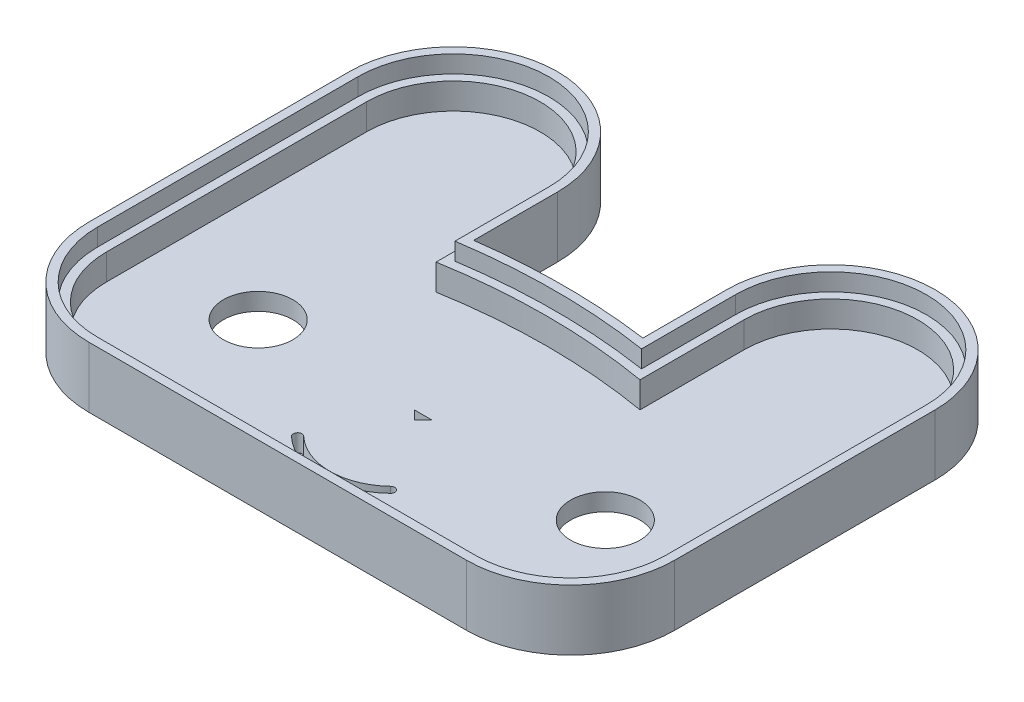
SolidWorks part; units mm, degrees
ref_plane "前视基准面" through (0, 0, 0) normal (0, 0, 1) x (1, 0, 0)
ref_plane "上视基准面" through (0, 0, 0) normal (0, 1, 0) x (1, 0, 0)
ref_plane "右视基准面" through (0, 0, 0) normal (1, 0, 0) x (0, 0, -1)
sketch "草图1" plane through (0, 0, 0) normal (0, 1, 0) x (1, 0, 0)
  line L0 (-12.3332, 12.48) -> (-12.3332, 24.48)
  line L1 (-2.3332, -15.52) -> (41.1668, -15.52)
  line L2 (-12.3332, -5.52) -> (-12.3332, 12.48)
  line L3 (-2.3332, -17.52) -> (41.1668, -17.52)
  line L4 (51.1668, -5.52) -> (51.1668, 12.48)
  line L5 (7.6668, 12.48) -> (7.6668, 24.48)
  line L6 (51.1668, 24.48) -> (51.1668, 12.48)
  line L7 (31.1668, 24.48) -> (31.1668, 12.48)
  line L8 (-12.3332, 24.48) -> (7.6668, 24.48) construction
  line L9 (31.1668, 24.48) -> (51.1668, 24.48) construction
  line L10 (53.1668, -5.52) -> (53.1668, 12.48)
  line L11 (53.1668, 24.48) -> (53.1668, 12.48)
  line L12 (29.1668, 24.48) -> (29.1668, 14.8124)
  line L13 (9.6668, 14.8124) -> (9.6668, 24.48)
  line L14 (-14.3332, 12.48) -> (-14.3332, 24.48)
  line L15 (-14.3332, -5.52) -> (-14.3332, 12.48)
  line L16 (30.1668, 24.48) -> (30.1668, 13.656)
  line L17 (52.1668, 24.48) -> (52.1668, 12.48)
  line L18 (52.1668, -5.52) -> (52.1668, 12.48)
  line L19 (-2.3332, -16.52) -> (41.1668, -16.52)
  line L20 (-13.3332, -5.52) -> (-13.3332, 12.48)
  line L21 (-13.3332, 12.48) -> (-13.3332, 24.48)
  line L22 (8.6668, 13.656) -> (8.6668, 24.48)
  arc A0 (7.6668, 24.48) -> (-12.3332, 24.48) centre (-2.3332, 24.48) ccw
  arc A1 (51.1668, 24.48) -> (31.1668, 24.48) centre (41.1668, 24.48) ccw
  arc A2 (41.1668, -15.52) -> (51.1668, -5.52) centre (41.1668, -5.52) ccw
  arc A3 (-12.3332, -5.52) -> (-2.3332, -15.52) centre (-2.3332, -5.52) ccw
  arc A4 (7.6668, 12.48) -> (31.1668, 12.48) centre (19.4168, -56.0512) cw
  arc A5 (41.1668, -17.52) -> (53.1668, -5.52) centre (41.1668, -5.52) ccw
  arc A6 (53.1668, 24.48) -> (29.1668, 24.48) centre (41.1668, 24.48) ccw
  arc A7 (9.6668, 14.8124) -> (29.1668, 14.8124) centre (19.4168, -56.0512) cw
  arc A8 (9.6668, 24.48) -> (-14.3332, 24.48) centre (-2.3332, 24.48) ccw
  arc A9 (-14.3332, -5.52) -> (-2.3332, -17.52) centre (-2.3332, -5.52) ccw
  arc A10 (8.6668, 13.656) -> (30.1668, 13.656) centre (19.4168, -56.0512) cw
  arc A11 (52.1668, 24.48) -> (30.1668, 24.48) centre (41.1668, 24.48) ccw
  arc A12 (41.1668, -16.52) -> (52.1668, -5.52) centre (41.1668, -5.52) ccw
  arc A13 (-13.3332, -5.52) -> (-2.3332, -16.52) centre (-2.3332, -5.52) ccw
  arc A14 (8.6668, 24.48) -> (-13.3332, 24.48) centre (-2.3332, 24.48) ccw
extrude "凸台-拉伸1" add sketch "草图1" along normal blind 2 contours A4 L5 A0 L0 L2 A3 L1 A2 L4 L6 A1 L7 region at (19.4168, 0, -6.2729)
extrude "凸台-拉伸2" add sketch "草图1<3>" along normal blind 5 contours L2 L0 A0 L5 A4 L7 A1 L6 L4 A2 L1 A3 | L20 L21 A14 L22 A10 L16 A11 L17 L18 A12 L19 A13
sketch "草图1<3>" plane through (0, 0, 0) normal (0, 1, 0) x (1, 0, 0) same geometry as "草图1"
extrude "凸台-拉伸3" add sketch "草图1<4>" along normal blind 7 contours A9 L3 A5 L10 L11 A6 L12 A7 L13 A8 L14 L15 | A13 L19 A12 L18 L17 A11 L16 A10 L22 A14 L21 L20
sketch "草图1<4>" plane through (0, 0, 0) normal (0, 1, 0) x (1, 0, 0) same geometry as "草图1"
sketch "草图2" plane through (0, 0, 0) normal (0, -1, 0) x (1, 0, 0)
  line L0 (-0.3332, 9.52) -> (40.1668, 9.52) construction
  line L1 (14.4168, 11.52) -> (24.4168, 11.52) construction
  line L2 (-2.3332, 0.52) -> (41.1668, 0.52)
  line L3 (0.1668, 0.52) -> (40.1668, 0.52) construction
  line L4 (19.1668, 0.52) -> (18.1668, 0.52)
  line L5 (-14.3332, 5.52) -> (-14.3332, -24.48) construction
  line L6 (53.1668, 5.52) -> (53.1668, -24.48) construction
  line L7 (20.1668, 0.52) -> (19.1668, 0.52)
  line L8 (19.1668, 1.52) -> (18.1668, 0.52)
  line L9 (19.1668, 1.52) -> (20.1668, 0.52)
  line L12 (14.4168, 9.52) -> (24.4168, 9.52) construction
  line L14 (24.4168, 9.52) -> (25.1065, 10.2441) construction
  line L15 (14.4168, 9.52) -> (13.7272, 10.2441) construction
  line L16 (24.7789, 9.1751) -> (25.4685, 9.8993) construction
  line L17 (14.0548, 9.1751) -> (13.3651, 9.8993) construction
  line L18 (-0.3332, 0.52) -> (40.1668, 0.52) construction
  circle A0 centre (0.1668, 0.52) radius 4
  circle A1 centre (40.1668, 0.52) radius 4
  arc A2 (24.4168, 9.52) -> (14.4168, 9.52) centre (19.4168, 4.27) ccw
  arc A3 (25.1065, 10.2441) -> (13.7272, 10.2441) centre (19.4168, 4.27) ccw
  arc A4 (25.1065, 10.2441) -> (24.4168, 9.52) centre (24.7616, 9.882) cw
  arc A5 (14.4168, 9.52) -> (13.7272, 10.2441) centre (14.072, 9.882) cw
  dimension "D3" = 13
  dimension "D9" = 10
  dimension "D10" = 2
  dimension "D14" = 40
  dimension "D2" = 14.5
  dimension "D1" = 17
  dimension "D8" = 9
  dimension "D11" = 1
  dimension "D12" = 0.5
  dimension "D13" = 0.5
extrude "切除-拉伸1" cut sketch "草图2" against normal blind 9 contours A1 | L7 | A0 | A2 A5 A3 A4 region at (40.1668, 0, 4.4068) region at (19.1668, 0, 0.8533) region at (-3.72, 0, 0.52)
